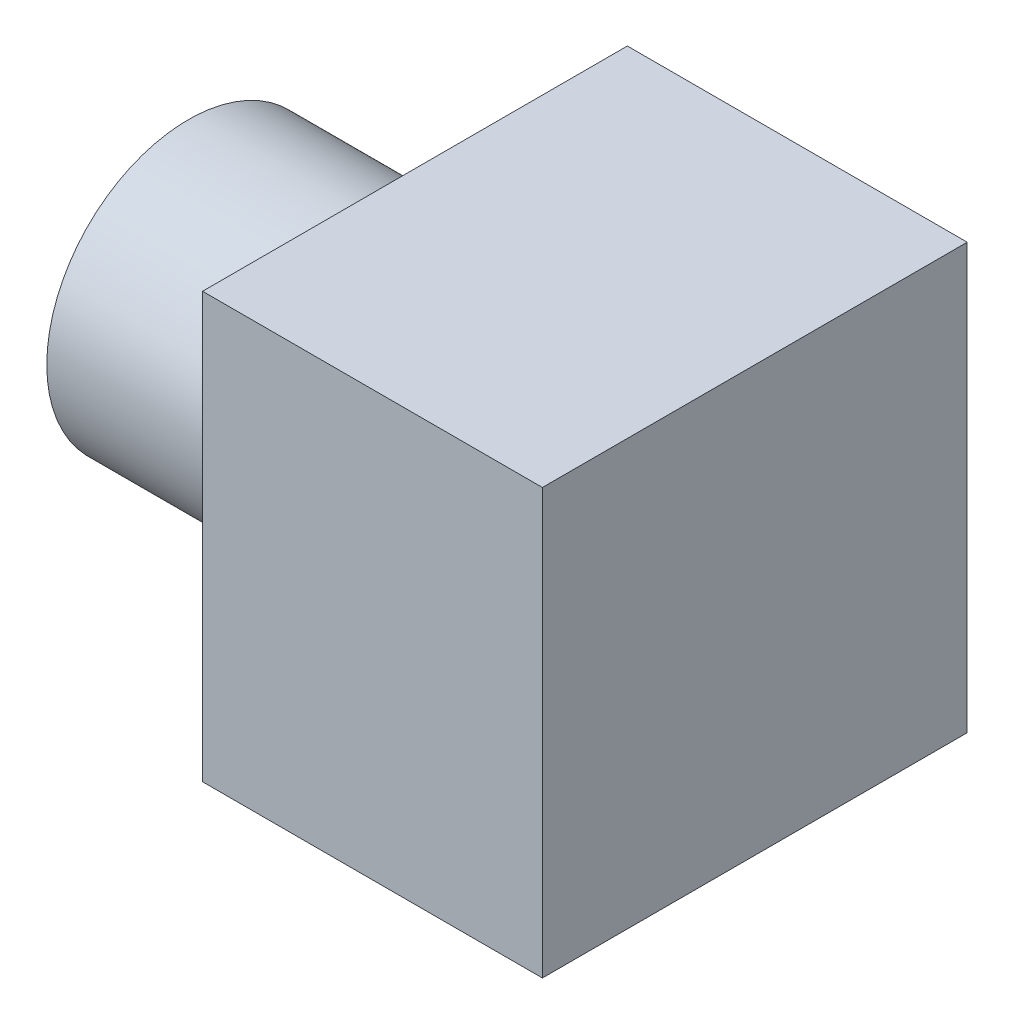
SolidWorks part; units mm, degrees
ref_plane "Front Plane" through (0, 0, 0) normal (0, 0, 1) x (1, 0, 0)
ref_plane "Top Plane" through (0, 0, 0) normal (0, 1, 0) x (1, 0, 0)
ref_plane "Right Plane" through (0, 0, 0) normal (1, 0, 0) x (0, 0, -1)
sketch "Sketch2" plane through (-36.1378, 0, 0) normal (-1, 0, 0) x (0, 0, 1)
  circle A0 centre (-25, -31.6006) radius 5
extrude "Boss-Extrude1" add sketch "Sketch2" along normal blind 8
sketch "Sketch3" plane through (-36.1378, 0, 0) normal (1, 0, 0) x (0, 0, -1)
  line L1 (17.5, -24.1006) -> (32.5, -24.1006)
  line L2 (17.5, -24.1006) -> (17.5, -39.1006)
  line L3 (17.5, -39.1006) -> (32.5, -39.1006)
  line L4 (32.5, -24.1006) -> (32.5, -39.1006)
  circle A0 centre (25, -31.6006) radius 5 construction
  dimension "D1" = 7.5
  dimension "D2" = 15
  dimension "D3" = 7.5
  dimension "D4" = 15
extrude "Boss-Extrude2" add sketch "Sketch3" along normal blind 12
sketch "Sketch4" plane through (-44.1378, 0, 0) normal (-1, 0, 0) x (0, 0, 1)
  circle A2 centre (-25, -31.6006) radius 4
  circle A3 centre (-25, -31.6006) radius 4
  dimension "D1" = 1
extrude "Cut-Extrude1" cut sketch "Sketch4" against normal blind 1
